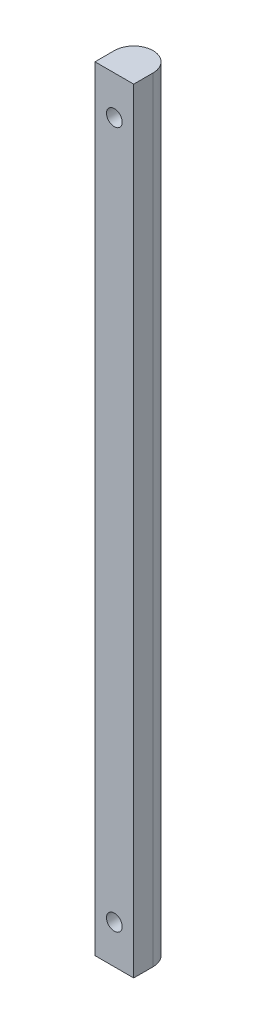
SolidWorks part; units mm, degrees
material "6061-T6 (SS)"
ref_plane "Front Plane" through (0, 0, 0) normal (0, 0, 1) x (1, 0, 0)
ref_plane "Top Plane" through (0, 0, 0) normal (0, 1, 0) x (1, 0, 0)
ref_plane "Right Plane" through (0, 0, 0) normal (1, 0, 0) x (0, 0, -1)
sketch "Sketch1" plane through (0, 0, 0) normal (0, 1, 0) x (1, 0, 0)
  line L0 (-3.175, 3.175) -> (-3.175, 0)
  line L1 (-3.175, 0) -> (3.175, 0)
  line L2 (3.175, 0) -> (3.175, 3.175)
  arc A0 (-3.175, 3.175) -> (3.175, 3.175) centre (0, 3.175) cw
  point P5 (0, 0)
  point P8 (0, 6.35)
  dimension "D2" = 3.175
  dimension "D1" = 6.35
  dimension "D3" = 6.35
extrude "Boss-Extrude1" add sketch "Sketch1" along normal mid plane 127
hole_wizard "#5-40 Tapped Hole1" positions "Sketch2" profile "Sketch3" tap size "#5-40" standard "ANSI Inch" end condition through all
sketch "Sketch2" plane through (0, 0, 0) normal (0, 0, 1) x (1, 0, 0)
  line L0 (-3.175, -63.5) -> (3.175, -63.5) construction
  point P2 (0, -57.15)
  dimension "D1" = 6.35
sketch "Sketch3" plane through (0, -57.15, 0) normal (1, 0, 0) x (0, -1, 0)
  line L0 (0, 0) -> (0, 6.35)
  line L1 (0, 6.35) -> (1.289, 6.35)
  line L2 (1.289, 6.35) -> (1.289, 0)
  line L5 (1.289, 0) -> (0, 0)
  line L11 (0, -6.35) -> (0, 107.95) construction
  dimension "Thru Tap Drill Dia." = 2.5781
  dimension "Thru Tap Drill Depth" = 6.35
cosmetic thread "Hole Thread1"
mirror "Mirror1" about plane through (0, 0, 0) normal (0, 1, 0) of "#5-40 Tapped Hole1"
cosmetic thread "Hole Thread2"
